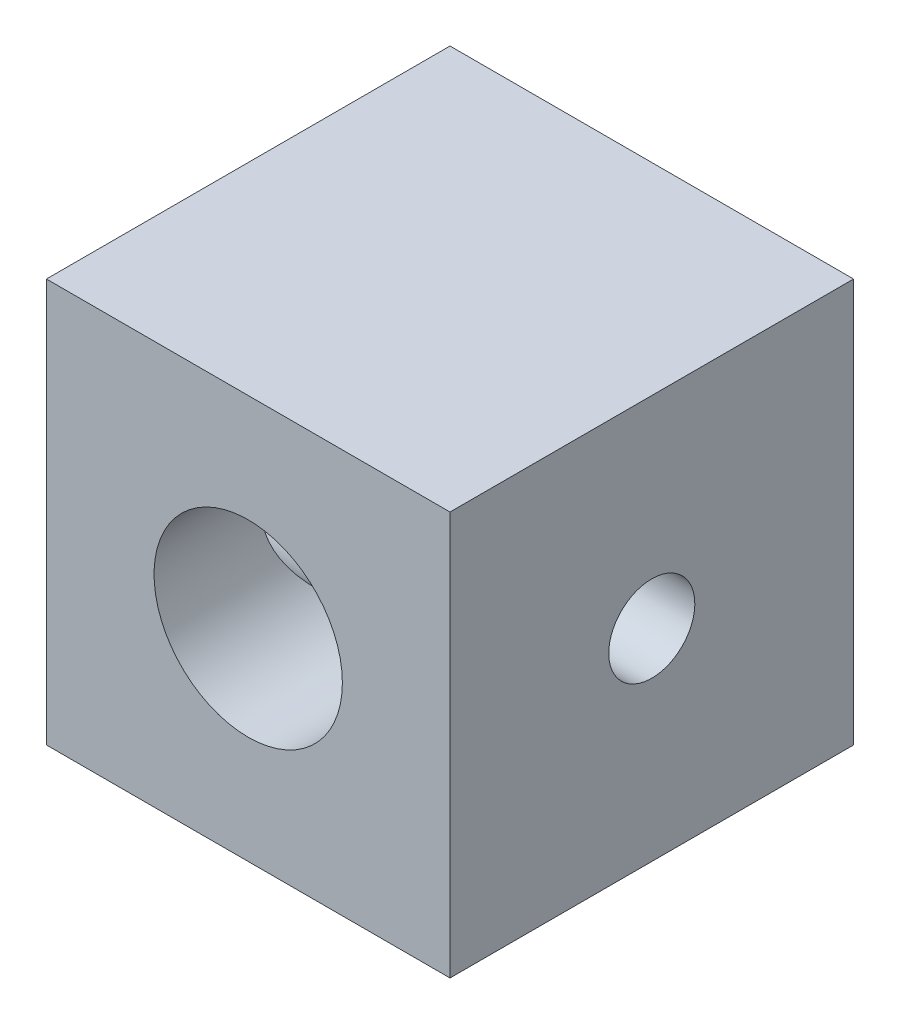
SolidWorks part; units mm, degrees
ref_plane "Plano frontal" through (0, 0, 0) normal (0, 0, 1) x (1, 0, 0)
ref_plane "Plano superior" through (0, 0, 0) normal (0, 1, 0) x (1, 0, 0)
ref_plane "Plano direito" through (0, 0, 0) normal (1, 0, 0) x (0, 0, -1)
sketch "Esboço1" plane through (0, 0, 0) normal (0, 0, 1) x (1, 0, 0)
  line L1 (-7.5, 7.5) -> (7.5, 7.5)
  line L2 (-7.5, 7.5) -> (-7.5, -7.5)
  line L3 (-7.5, -7.5) -> (7.5, -7.5)
  line L4 (7.5, 7.5) -> (7.5, -7.5)
  line L5 (-7.5, 7.5) -> (7.5, -7.5) construction
  line L6 (-7.5, -7.5) -> (7.5, 7.5) construction
  circle A0 centre (0, 0) radius 1.6
  circle A1 centre (0, 0) radius 3.5
  point P0 (0, 0)
  dimension "D1" = 3.2
  dimension "D3" = 7
  dimension "D2" = 15
extrude "Ressalto-extrusão1" add sketch "Esboço1" along normal mid plane 15 contours L4 L1 L2 L3 A1 region at (0, 7.2879, 0)
sketch "Esboço2" plane through (7.5, 0, 0) normal (1, 0, 0) x (0, 0, -1)
  line L0 (-7.5, 7.5) -> (7.5, -7.5) construction
  circle A0 centre (0, 0) radius 3.5
  circle A1 centre (0, 0) radius 1.6
  dimension "D1" = 3.2
  dimension "D2" = 7
extrude "Corte-extrusão1" cut sketch "Esboço2" against normal through all contours A0
sketch "Esboço4" plane through (0, 7.5, 0) normal (0, 1, 0) x (1, 0, 0)
  circle A0 centre (0, 0) radius 3.5
  circle A1 centre (0, 0) radius 1.6
  dimension "D1" = 7
  dimension "D2" = 3.2
extrude "Corte-extrusão2" [suppressed] cut sketch "Esboço4" against normal through all both and the other way through all contours A0
extrude "Ressalto-extrusão2" add sketch "Esboço1<3>" along normal blind 3 from surface contours A1 A0 region at (-3.401, 0, 0) starting at face at (3.5, 0, -7.5)
sketch "Esboço1<3>" plane through (0, 0, 0) normal (0, 0, 1) x (1, 0, 0) same geometry as "Esboço1"
extrude "Ressalto-extrusão3" add sketch "Esboço2<3>" against normal blind 3
sketch "Esboço2<3>" plane through (7.5, 0, 0) normal (1, 0, 0) x (0, 0, -1) same geometry as "Esboço2"
extrude "Ressalto-extrusão4" add sketch "Esboço4<3>" against normal blind 3
sketch "Esboço4<3>" plane through (0, 7.5, 0) normal (0, 1, 0) x (1, 0, 0) same geometry as "Esboço4"
